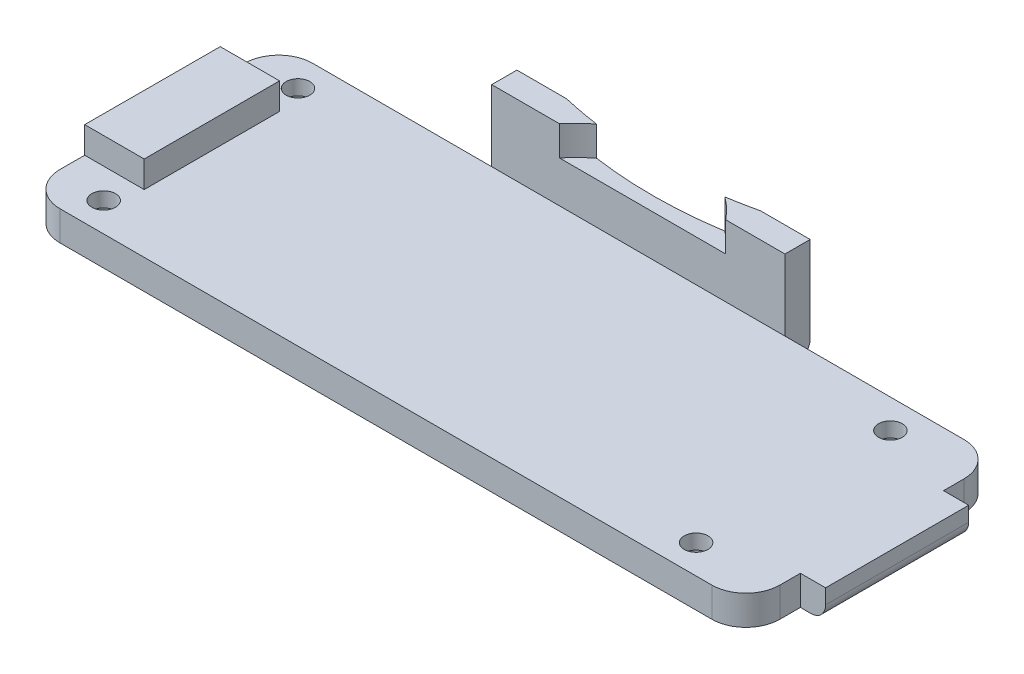
SolidWorks part; units mm, degrees
ref_plane "前视基准面" through (0, 0, 0) normal (0, 0, 1) x (1, 0, 0)
ref_plane "上视基准面" through (0, 0, 0) normal (0, 1, 0) x (1, 0, 0)
ref_plane "右视基准面" through (0, 0, 0) normal (1, 0, 0) x (0, 0, -1)
sketch "草图1" plane through (0, 0, 0) normal (0, 1, 0) x (1, 0, 0)
  line L0 (50.2965, 15.0388) -> (51.9956, 15.0385)
  line L1 (4.0195, 18.732) -> (47.9974, 18.7199)
  line L2 (50.2968, 16.4194) -> (50.2965, 15.0388)
  line L3 (50.2942, 5.38) -> (50.294, 3.9995)
  line L4 (47.9935, 1.7) -> (3.9936, 1.7)
  line L5 (1.6941, 4.0005) -> (1.7189, 16.4325)
  line L6 (51.9956, 15.0385) -> (51.9948, 5.3803)
  line L7 (50.2942, 5.38) -> (51.9948, 5.3803)
  arc A0 (4.0195, 18.732) -> (1.7189, 16.4325) centre (4.0189, 16.432) ccw
  arc A1 (1.6941, 4.0005) -> (3.9936, 1.7) centre (3.9941, 4) ccw
  arc A2 (50.2968, 16.4194) -> (47.9974, 18.7199) centre (47.9968, 16.4199) ccw
  arc A3 (47.9935, 1.7) -> (50.294, 3.9995) centre (47.994, 4) ccw
extrude "凸台-拉伸1" add sketch "草图1" along normal blind 2
sketch "草图3" plane through (0, 0, 0) normal (0, 1, 0) x (1, 0, 0)
  circle A0 centre (4.987, 16.7698) radius 1.4
  circle A1 centre (4.984, 3.6578) radius 1.4
  circle A2 centre (44.9869, 16.7607) radius 1.4
  circle A3 centre (44.9839, 3.6487) radius 1.4
extrude "切除-拉伸2" cut sketch "草图3" along normal blind 1
sketch "草图4" plane through (0, 2, 0) normal (0, 1, 0) x (1, 0, 0)
  circle A0 centre (44.9839, 3.6487) radius 0.8
  circle A1 centre (44.9869, 16.7607) radius 0.8
  circle A2 centre (4.984, 3.6578) radius 0.8
  circle A3 centre (4.987, 16.7698) radius 0.8
extrude "切除-拉伸3" cut sketch "草图4" against normal blind 7
fillet "圆角1" radius 1 1 edges at (51.9952, 0, -10.2094)
sketch "草图5" plane through (0, 2, 0) normal (0, 1, 0) x (1, 0, 0)
  line L0 (1.7157, 14.7956) -> (5.7157, 14.7956)
  line L1 (5.7157, 14.7956) -> (5.7157, 5.6605)
  line L2 (5.7157, 5.6605) -> (1.6974, 5.6605)
  line L3 (1.6974, 5.6605) -> (1.7157, 14.7956)
extrude "凸台-拉伸2" add sketch "草图5" along normal blind 1.79
sketch "草图6" plane through (0, 0, 0) normal (0, 1, 0) x (1, 0, 0)
  line L4 (35.9088, 20.4232) -> (35.9084, 18.7232)
  line L5 (16.1088, 20.4287) -> (16.1084, 18.7287)
  line L6 (35.9088, 20.4232) -> (16.1088, 20.4287)
  line L7 (16.1084, 18.7287) -> (35.9084, 18.7232)
extrude "凸台-拉伸3" add sketch "草图6" along normal blind 6.8
sketch "草图7" plane through (0, 6.8, 0) normal (0, 1, 0) x (1, 0, 0)
  line L0 (20.4546, 18.4275) -> (32.1379, 18.4243)
  arc A0 (32.1379, 18.4243) -> (20.4546, 18.4275) centre (26.2951, 14.2169) ccw
extrude "切除-拉伸4" cut sketch "草图7" against normal blind 2
sketch "草图8" plane through (0, 2, 0) normal (0, 1, 0) x (1, 0, 0)
  circle A0 centre (26.0152, 48.5808) radius 28.9053
extrude "切除-拉伸5" cut sketch "草图8" against normal blind 5 and the other way blind 9
fillet "圆角2" radius 1 3 edges at (34.23, 0, -20.4237) (17.7863, 0, -20.4282) (26.0073, 0, -19.6755)
